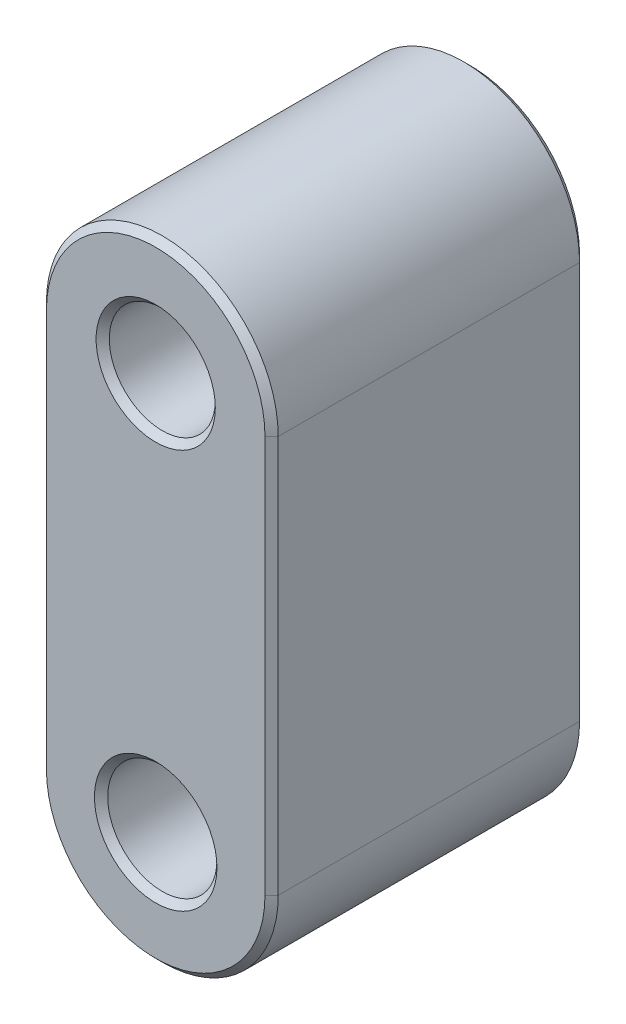
SolidWorks part; units mm, degrees
ref_plane "Front" through (0, 0, 0) normal (0, 0, 1) x (1, 0, 0)
ref_plane "Top" through (0, 0, 0) normal (0, 1, 0) x (1, 0, 0)
ref_plane "Right" through (0, 0, 0) normal (1, 0, 0) x (0, 0, -1)
sketch "Sketch1" plane through (0, 0, 0) normal (0, 0, 1) x (1, 0, 0)
  line L3 (-3.5, 0) -> (-1.6, 0) construction
  line L23 (1.65, -12) -> (3.55, -12) construction
  line L33 (-3.5, 0) -> (-3.5, -12)
  line L34 (3.5, -12) -> (3.5, 0)
  circle A0 centre (0, 0) radius 3.5 construction
  circle A3 centre (0, 0) radius 1.6
  circle A12 centre (0, -12) radius 1.65
  circle A13 centre (0, -12) radius 4.25 construction
  arc A22 (-3.5, 0) -> (3.5, 0) centre (0, 0) cw
  arc A28 (-3.5, -12) -> (3.5, -12) centre (0, -12) ccw
  dimension "D1" = 3.2
  dimension "D3" = 8.5
  dimension "D6" = 3.3
  dimension "D7" = 3.5
  dimension "D2" = 1.9
  dimension "D5" = 12
extrude "Boss-Extrude1" add sketch "Sketch1" along normal mid plane 9.5 contours A3 region at (0, -5.9711, 0)
sketch "Sketch2" plane through (0, 0, 0) normal (0, 0, 1) x (1, 0, 0)
  line L0 (-3.493, -12.2206) -> (-4.3536, 1.4044)
  line L1 (0, 0) -> (0, 8.0844) construction
  line L2 (0, 0) -> (-0.7607, 1.6314) construction
  line L3 (-0.7607, 1.6314) -> (-2.1131, 4.5315) construction
  line L4 (-2.1131, 4.5315) -> (-2.2821, 4.8941) construction
  line L5 (2.8351, 1.8045) -> (3.5, -12)
  line L6 (3.5, -12) -> (3.5, 0) construction
  arc A0 (-4.3536, 1.4044) -> (2.8351, 1.8045) centre (-0.7607, 1.6314) cw
  circle A1 centre (0, 0) radius 5 construction
  arc A2 (-3.5, -12) -> (3.5, -12) centre (0, -12) ccw construction
  dimension "D2" = 10
  dimension "D4" = 3.6
  dimension "D1" = 0.4
  dimension "D3" = 25
extrude "Spring" [suppressed] add sketch "Sketch2" along normal through all and the other way through all thin thin type one direction wall 1
fillet "Spring Inside Fillets" [suppressed] radius 0.25
chamfer "Deburs" [suppressed] distance 0.2 angle 45
sketch "Sketch3" [suppressed] plane through (-4.2479, -0.2683, 0) normal (-0.998, -0.063, 0) x (0, 0, 1)
  line L1 (0, -0.8239) -> (0, -9.4761) construction
  line L6 (4.55, 1.6761) -> (-4.55, 1.6761) construction
  line L8 (4.55, -11.9761) -> (-4.55, -11.9761) construction
  dimension "D1" = 2.5
  dimension "D2" = 2.5
sketch "Sketch4" [suppressed] plane through (-4.2479, -0.2683, 0) normal (-0.998, -0.063, 0) x (0, 0, 1)
  line L0 (0, -0.8239) -> (0, -9.4761)
  line L1 (-2, -2.8239) -> (0, -0.8239)
  line L2 (0, -0.8239) -> (2, -2.8239)
  line L3 (0, -0.8239) -> (0, -9.4761) construction
  line L6 (0, -11.9341) -> (0, 0.0312) construction
  dimension "D1" = 45
  dimension "D2" = 2
extrude "Arrow Point" [suppressed] add sketch "Sketch4" along normal blind 0.2 draft 55 thin contours L1 | L2 thin type one direction wall 0.8
sketch "Sketch5" [suppressed] plane through (-4.2479, -0.2683, 0) normal (-0.998, -0.063, 0) x (0, 0, 1)
  line L0 (0, -1.2279) -> (0, -9.4761)
  line L1 (0, -0.8239) -> (0, -9.4761) construction
extrude "Arrow Shaft" [suppressed] add sketch "Sketch5" along normal blind 0.2 draft 55 thin thin type mid plane wall 0.8
chamfer "Deburs no Spring" distance 0.2 angle 45 12 edges at (0, -15.5, -4.75) (3.5, -6, -4.75) (0, 3.5, -4.75) (-3.5, -6, -4.75) (1.65, -12, -4.75) (1.6, 0, -4.75) (0, 3.5, 4.75) (3.5, -6, 4.75) (0, -15.5, 4.75) (-3.5, -6, 4.75) (1.65, -12, 4.75) (1.6, 0, 4.75)
equation "\"D1@Sketch1\"=\"Clearance Hole Diameter@Box Assy.Assembly\"+.05mm"
equation "\"D6@Sketch1\"=\"Clearance Hole Diameter@Box Assy.Assembly\"+.15mm"
